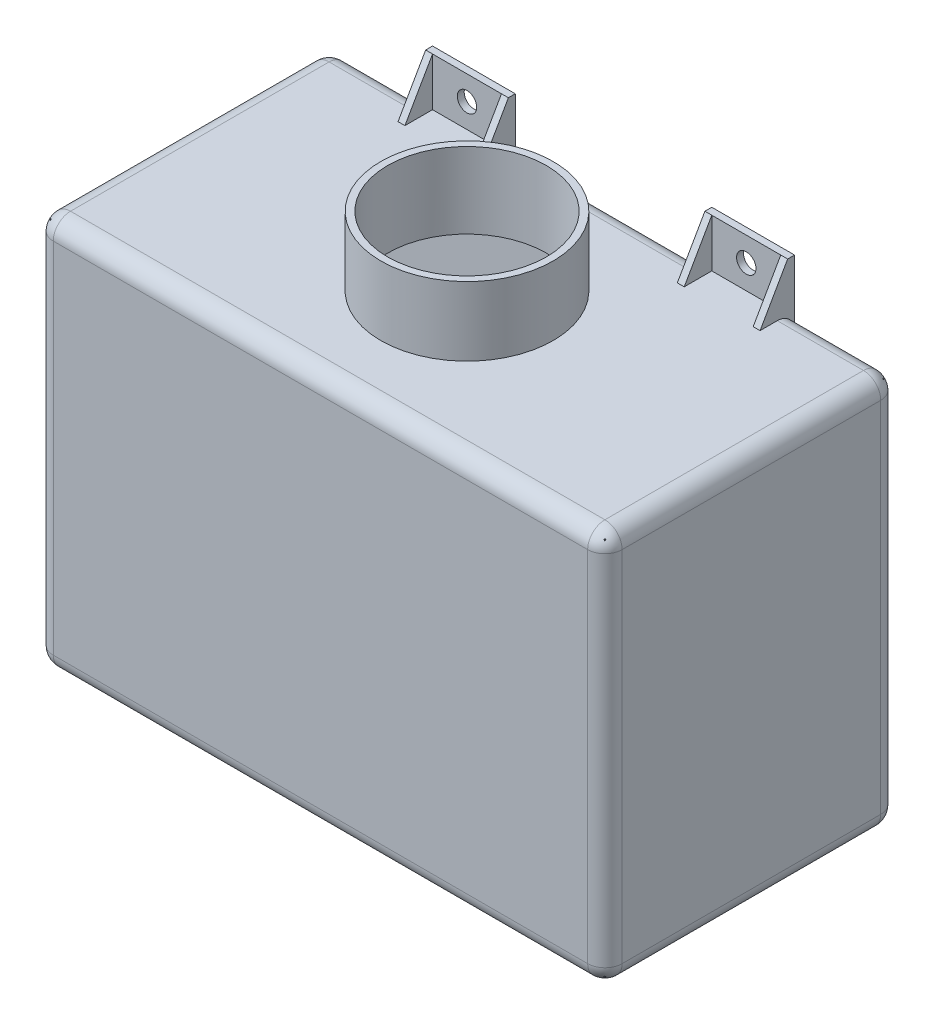
SolidWorks part; units mm, degrees
material "PE Low/Medium Density"
ref_plane "X-Y Datum" through (0, 0, 0) normal (0, 0, 1) x (1, 0, 0)
ref_plane "X-Z Datum" through (0, 0, 0) normal (0, 1, 0) x (1, 0, 0)
ref_plane "Y-Z Datum" through (0, 0, 0) normal (1, 0, 0) x (0, 0, -1)
sketch "Sketch1" plane through (0, 0, 0) normal (0, 1, 0) x (1, 0, 0)
  line L1 (104.775, 53.975) -> (-104.775, 53.975)
  line L2 (104.775, 53.975) -> (104.775, -53.975)
  line L3 (104.775, -53.975) -> (-104.775, -53.975)
  line L4 (-104.775, 53.975) -> (-104.775, -53.975)
  line L5 (104.775, 53.975) -> (-104.775, -53.975) construction
  line L6 (104.775, -53.975) -> (-104.775, 53.975) construction
  point P0 (0, 0)
  dimension "D1" = 209.55
  dimension "D2" = 107.95
extrude "Boss-Extrude1" add sketch "Sketch1" along normal blind 144.78
sketch "Sketch2" plane through (0, 144.78, 0) normal (0, 1, 0) x (1, 0, 0)
  circle A0 centre (0, 0) radius 31.75
  dimension "D1" = 63.5
extrude "Boss-Extrude2" add sketch "Sketch2" along normal blind 25.4
sketch "Sketch8" plane through (0, 0, 0) normal (0, -1, 0) x (1, 0, 0)
  line L0 (-104.775, 0) -> (104.775, 0)
  line L1 (-104.775, -53.975) -> (-104.775, 53.975) construction
  line L2 (104.775, 53.975) -> (104.775, -53.975) construction
  circle A0 centre (41.275, 0) radius 6.35
  dimension "D1" = 12.7
  dimension "D2" = 63.5
extrude "Boss-Extrude5" add sketch "Sketch8" along normal blind 30.48 contours A0
sketch "Sketch3" plane through (0, 144.78, 0) normal (0, 1, 0) x (1, 0, 0)
  line L0 (-66.675, 53.975) -> (-66.675, 41.275)
  line L1 (104.775, 53.975) -> (-104.775, 53.975) construction
  line L2 (-66.675, 41.275) -> (-64.135, 41.275)
  line L3 (-64.135, 41.275) -> (-64.135, 51.435)
  line L4 (-64.135, 51.435) -> (-38.735, 51.435)
  line L5 (-38.735, 51.435) -> (-38.735, 41.275)
  line L6 (-38.735, 41.275) -> (-36.195, 41.275)
  line L7 (-36.195, 41.275) -> (-36.195, 53.975)
  line L8 (-36.195, 53.975) -> (-66.675, 53.975)
  line L9 (-104.775, 53.975) -> (-104.775, -53.975) construction
  line L10 (0, 53.975) -> (0, -53.975) construction
  line L11 (-104.775, -53.975) -> (104.775, -53.975) construction
  line L12 (36.195, 53.975) -> (66.675, 53.975)
  line L13 (36.195, 41.275) -> (36.195, 53.975)
  line L14 (38.735, 41.275) -> (36.195, 41.275)
  line L15 (38.735, 51.435) -> (38.735, 41.275)
  line L16 (64.135, 51.435) -> (38.735, 51.435)
  line L17 (64.135, 41.275) -> (64.135, 51.435)
  line L18 (66.675, 41.275) -> (64.135, 41.275)
  line L19 (66.675, 53.975) -> (66.675, 41.275)
  dimension "D1" = 12.7
  dimension "D2" = 2.54
  dimension "D3" = 2.54
  dimension "D4" = 38.1
  dimension "D5" = 68.58
extrude "Boss-Extrude3" add sketch "Sketch3" along normal blind 17.78
sketch "Sketch5" plane through (38.735, 0, 0) normal (1, 0, 0) x (0, 0, -1)
  line L0 (41.275, 144.78) -> (51.435, 162.56)
  line L4 (41.275, 144.78) -> (51.435, 144.78)
  line L5 (51.435, 144.78) -> (51.435, 162.56)
  line L6 (51.435, 162.56) -> (41.275, 162.56)
  line L7 (41.275, 162.56) -> (41.275, 144.78)
  line L8 (41.275, 144.78) -> (51.435, 144.78)
  line L9 (51.435, 144.78) -> (51.435, 162.56)
  line L10 (51.435, 162.56) -> (41.275, 162.56)
  line L11 (41.275, 162.56) -> (41.275, 144.78)
  line M7 (51.435, 162.56) -> (41.275, 162.56)
  line M8 (41.275, 162.56) -> (41.275, 144.78)
  dimension "D1" = 0
extrude "Cut-Extrude2" cut sketch "Sketch5" against normal through all both and the other way through all contours L0 M8 M7 region at (38.735, 156.6333, -44.6617)
sketch "Sketch7" plane through (0, 0, 0) normal (0, -1, 0) x (1, 0, 0)
  line L0 (0, 53.975) -> (0, -53.975) construction
  line L1 (-104.775, 53.975) -> (104.775, 53.975) construction
  line L2 (104.775, -53.975) -> (-104.775, -53.975) construction
  line L3 (-15.24, -41.275) -> (-15.24, -53.975)
  line L4 (15.24, -41.275) -> (15.24, -53.975)
  line L5 (-15.24, -53.975) -> (15.24, -53.975)
  line L6 (-12.7, -41.275) -> (-12.7, -51.435)
  line L7 (12.7, -41.275) -> (12.7, -51.435)
  line L8 (-15.24, -41.275) -> (-12.7, -41.275)
  line L9 (-12.7, -51.435) -> (12.7, -51.435)
  line L10 (12.7, -41.275) -> (15.24, -41.275)
  line L11 (15.24, 53.975) -> (15.24, -53.975) construction
  line L12 (12.7, 53.975) -> (12.7, -53.975) construction
  line L13 (-12.7, 53.975) -> (-12.7, -53.975) construction
  line L14 (-15.24, 53.975) -> (-15.24, -53.975) construction
  line L15 (-15.24, -51.435) -> (15.24, -51.435) construction
  dimension "D5" = 12.7
  dimension "D6" = 2.54
  dimension "D1" = 15.24
  dimension "D2" = 15.24
  dimension "D3" = 12.7
  dimension "D4" = 12.7
extrude "Boss-Extrude4" add sketch "Sketch7" along normal blind 30.48
shell "Shell1" thickness 2.54 removed face at (0, 170.18, 31.75) removed face at (41.275, -30.48, -6.35)
sketch "Sketch9" plane through (-12.7, 0, 0) normal (1, 0, 0) x (0, 0, -1)
  line L5 (41.275, 0) -> (51.435, -30.48)
  line L10 (51.435, -30.48) -> (41.275, -30.48) construction
  line L11 (41.275, -30.48) -> (41.275, 0) construction
  line L12 (51.435, -30.48) -> (41.275, -30.48)
  line L13 (41.275, -30.48) -> (41.275, 0)
extrude "Cut-Extrude4" cut sketch "Sketch9" against normal through all both and the other way through all
hole_wizard "1/4 Clearance Hole1" positions "3DSketch1" profile "Sketch6" hole size "1/4" standard "ANSI Inch" end condition through all
sketch3d "3DSketch1"
  line L0 (-64.135, 162.56, -51.435) -> (-38.735, 144.78, -51.435)
  line L1 (38.735, 162.56, -51.435) -> (64.135, 144.78, -51.435)
  line L6 (12.7, -30.48, -51.435) -> (-12.7, -30.48, -51.435) construction
  line L7 (12.7, -30.48, -51.435) -> (12.7, 0, -51.435) construction
  point P0 (-51.435, 153.67, -51.435)
  point P10 (51.435, 153.67, -51.435)
  point P18 (0, -20.32, -51.435)
  dimension "D1" = 10.16
  dimension "D2" = 12.7
sketch "Sketch6" plane through (-51.435, 153.67, -51.435) normal (1, 0, 0) x (0, -1, 0)
  line L0 (0, 0) -> (0, 2.54)
  line L1 (0, 2.54) -> (3.5712, 2.54)
  line L2 (3.5712, 2.54) -> (3.5712, 0)
  line L5 (3.5712, 0) -> (0, 0)
  line L11 (0, -6.35) -> (0, 107.95) construction
  dimension "Thru Hole Dia." = 7.1425
  dimension "Thru Hole Depth" = 2.54
fillet "Fillet1" radius 6.35 15 edges at (104.775, 144.78, 0) (104.775, 72.39, -53.975) (104.775, 0, 0) (0, 144.78, 53.975) (104.775, 72.39, 53.975) (0, 0, 53.975) (-104.775, 72.39, -53.975) (-104.775, 144.78, 0) (-104.775, 72.39, 53.975) (-104.775, 0, 0) (-60.0075, 0, -53.975) (60.0075, 0, -53.975) (0, 144.78, -53.975) (-85.725, 144.78, -53.975) (85.725, 144.78, -53.975)
